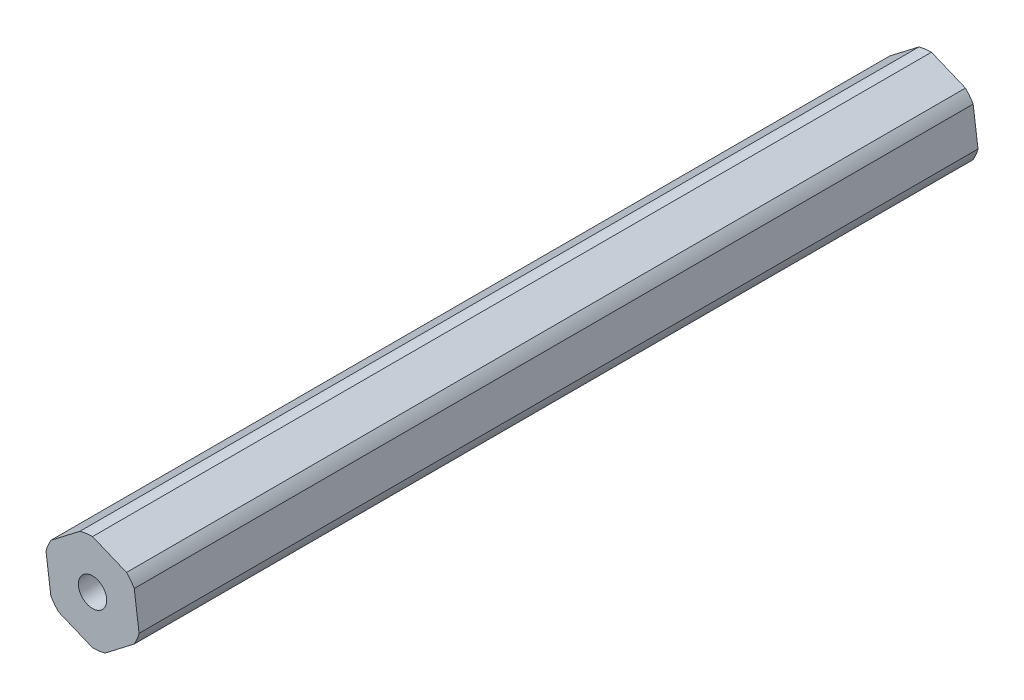
SolidWorks part; units mm, degrees
material "6061-T6 (SS)"
ref_plane "Front Plane" through (0, 0, 0) normal (0, 0, 1) x (1, 0, 0)
ref_plane "Top Plane" through (0, 0, 0) normal (0, 1, 0) x (1, 0, 0)
ref_plane "Right Plane" through (0, 0, 0) normal (1, 0, 0) x (0, 0, -1)
sketch "Sketch1" plane through (0, 0, 0) normal (0, 0, 1) x (1, 0, 0)
  line L1 (-1.7899, 6.6335) -> (-5.9502, 3.4354)
  line L2 (-6.6397, 1.7666) -> (-5.9502, -3.4353)
  line L3 (-4.8498, -4.8668) -> (0, -6.8707)
  line L4 (1.7899, -6.6335) -> (5.9502, -3.4354)
  line L5 (6.6397, -1.7666) -> (5.9502, 3.4353)
  line L6 (4.8498, 4.8668) -> (0, 6.8707)
  circle A0 centre (0, 0) radius 6.35 construction
  arc A1 (-5.9502, 3.4354) -> (-6.6397, 1.7666) centre (0, 0) ccw
  arc A2 (-5.9502, -3.4353) -> (-4.8498, -4.8668) centre (0, 0) ccw
  arc A3 (0, -6.8707) -> (1.7899, -6.6335) centre (0, 0) ccw
  arc A4 (5.9502, -3.4354) -> (6.6397, -1.7666) centre (0, 0) ccw
  arc A5 (5.9502, 3.4353) -> (4.8498, 4.8668) centre (0, 0) ccw
  arc A6 (0, 6.8707) -> (-1.7899, 6.6335) centre (0, 0) ccw
  dimension "D1" = 12.7
  dimension "D2" = 13.7414
extrude "Boss-Extrude1" add sketch "Sketch1" along normal blind 119.6975 contours L1 A1 L2 A2 L3 A3 L4 A4 L5 A5 L6 A6
hole_wizard "#10-32 Tapped Hole1" positions "Sketch4" profile "Sketch5" tap size "#10-32" standard "ANSI Inch"
sketch "Sketch4" plane through (0, 0, 119.6975) normal (0, 0, 1) x (1, 0, 0)
  point P0 (0, 0)
sketch "Sketch5" plane through (0, 0, 119.6975) normal (1, 0, 0) x (0, -1, 0)
  line L0 (0, 0) -> (0, 14.8277)
  line L1 (0, 14.8277) -> (2.0193, 13.6144)
  line L2 (2.0193, 13.6144) -> (2.0193, 0)
  line L5 (2.0193, 0) -> (0, 0)
  line L10 (0, 14.8277) -> (-2.0193, 13.6144) construction
  line L11 (0, -6.35) -> (0, 107.95) construction
  dimension "Tap Drill Dia." = 4.0386
  dimension "Tap Drill Depth" = 13.6144
  dimension "Drill Angle" = 118
cosmetic thread "Hole Thread3" parameters "D1"=9.652, "D2"=4.826
sketch "Sketch8" plane through (0, 0, 0) normal (0, 0, -1) x (-1, 0, 0)
  point P0 (0, 0)
hole_wizard "1/4-20 Tapped Hole2" positions "Sketch11" profile "Sketch12" tap size "1/4-20" standard "ANSI Inch"
sketch "Sketch11" plane through (0, 0, 0) normal (0, 0, -1) x (-1, 0, 0)
  point P0 (0, 0)
cosmetic thread "Hole Thread5" parameters "D1"=12.7, "D2"=6.35
sketch "Sketch12" plane through (0, 0, 0) normal (1, 0, 0) x (0, 1, 0)
  line L0 (0, 0) -> (0, 18.0438)
  line L1 (0, 18.0438) -> (2.5527, 16.51)
  line L2 (2.5527, 16.51) -> (2.5527, 0)
  line L5 (2.5527, 0) -> (0, 0)
  line L10 (0, 18.0438) -> (-2.5527, 16.51) construction
  line L11 (0, -6.35) -> (0, 107.95) construction
  dimension "Tap Drill Dia." = 5.1054
  dimension "Tap Drill Depth" = 16.51
  dimension "Drill Angle" = 118
